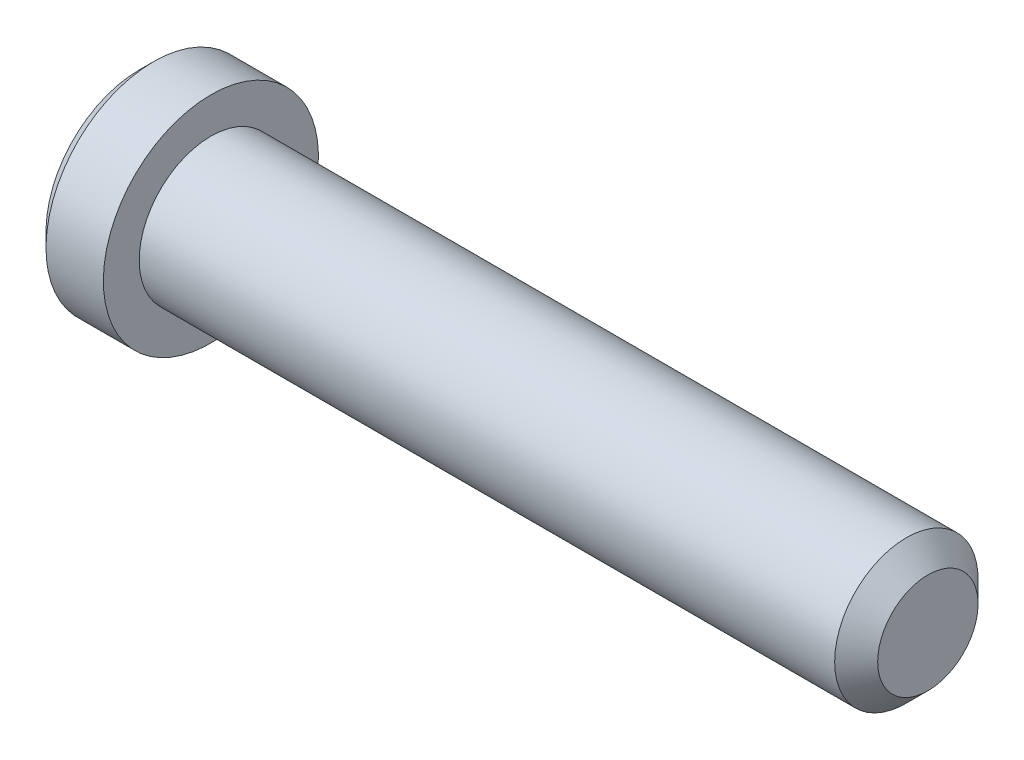
SolidWorks part; units mm, degrees
ref_plane "Front Plane" through (0, 0, 0) normal (0, 0, 1) x (1, 0, 0)
ref_plane "Top Plane" through (0, 0, 0) normal (0, 1, 0) x (1, 0, 0)
ref_plane "Right Plane" through (0, 0, 0) normal (1, 0, 0) x (0, 0, -1)
sketch "Sketch1" plane through (0, 0, 0) normal (0, 0, 1) x (1, 0, 0)
  line L0 (15.875, 0) -> (-15.875, 0) construction
  line L1 (15.875, 3.175) -> (15.875, -3.175) construction
  line L2 (-15.875, 4.7625) -> (-15.875, -4.7625) construction
  line L3 (-15.875, 4.7625) -> (-18.415, 4.7625) construction
  line L4 (-18.415, 4.7625) -> (-19.05, 4.1275) construction
  line L5 (-19.05, 4.1275) -> (-19.05, -4.1275) construction
  line L6 (-19.05, -4.1275) -> (-18.415, -4.7625) construction
  line L7 (-18.415, -4.7625) -> (-15.875, -4.7625) construction
  point P7 (-16.6624, 0)
  point P12 (10.795, -3.175)
  dimension "D1" = 45
  dimension "Dec." = 6.35
  dimension "Length" = 31.75
  dimension "Head Dia" = 9.525
  dimension "Head Height" = 3.175
  dimension "Hex Depth" = 2.3876
  dimension "Chamfer" = 0.635
  dimension "D2" = 5.08
ref_plane "Plane1" through (15.875, 0, 0) normal (1, 0, 0) x (0, 0, -1)
ref_plane "Plane2" through (-19.05, 0, 0) normal (1, 0, 0) x (0, 0, -1)
sketch "Sketch2" plane through (15.875, 0, 0) normal (1, 0, 0) x (0, 0, -1)
  circle A0 centre (0, 0) radius 3.175
extrude "Boss-Extrude1" add sketch "Sketch2" against normal up to vertex (31.75 mm away) up to point (-15.875, 0, 0)
sketch "Sketch3" plane through (15.875, 0, 0) normal (1, 0, 0) x (0, 0, -1)
  circle A0 centre (0, 0) radius 3.175 construction
  circle A1 centre (0, 0) radius 3.175
curve "Helix/Spiral1" [suppressed] pitch 1.27 height 33.02 turns 26 parameters "Pitch"=1.27
chamfer "Chamfer1" distance 0.9525 angle 45 1 edges at (15.875, 0, -3.175)
sketch "Sketch5" plane through (0, 0, 0) normal (0, 0, 1) x (1, 0, 0)
  line L0 (15.3194, 3.175) -> (16.4306, 3.175)
  line L1 (16.4306, 3.175) -> (15.9544, 2.3501)
  line L2 (15.9544, 2.3501) -> (15.7956, 2.3501)
  line L3 (15.7956, 2.3501) -> (15.3194, 3.175)
  line L4 (15.875, 2.3501) -> (15.875, 3.175) construction
  line L5 (15.5575, 2.7626) -> (16.1925, 2.7626) construction
  dimension "D1" = 60
  dimension "D2" = 0.635
  dimension "D3" = 0.1588
sweep "Cut-Sweep1" [suppressed] cut profiles "Sketch5" path "Helix/Spiral1"
sketch "Sketch4" plane through (-19.05, 0, 0) normal (1, 0, 0) x (0, 0, -1)
  line L0 (-4.7625, 0.7937) -> (4.7625, 0.7937) construction
  line L1 (0, 1.8331) -> (-1.5875, 0.9165)
  line L2 (-1.5875, 0.9165) -> (-1.5875, -0.9165)
  line L3 (-1.5875, -0.9165) -> (0, -1.8331)
  line L4 (0, -1.8331) -> (1.5875, -0.9165)
  line L5 (1.5875, -0.9165) -> (1.5875, 0.9165)
  line L6 (1.5875, 0.9165) -> (0, 1.8331)
  line L7 (0, 0) -> (0, 0.7937) construction
  circle A0 centre (0, 0) radius 1.5875 construction
  dimension "Hex Size" = 3.175
  dimension "D1" = 9.525
  dimension "D2" = 0.7937
sketch "Sketch6" plane through (0, 0, 0) normal (0, 0, 1) x (1, 0, 0)
  line L0 (-18.415, 4.7625) -> (-19.05, 4.1275) construction
  line L1 (-15.875, 4.7625) -> (-18.415, 4.7625) construction
  line L2 (-15.875, 4.7625) -> (-15.875, -4.7625) construction
  line L3 (-19.05, 4.1275) -> (-19.05, -4.1275) construction
  line L4 (-18.415, 4.7625) -> (-19.05, 4.1275)
  line L5 (-15.875, 4.7625) -> (-18.415, 4.7625)
  line L6 (-15.875, 4.7625) -> (-15.875, 0)
  line L7 (-19.05, 4.1275) -> (-19.05, 0)
  line L8 (-15.875, 0) -> (-19.05, 0) construction
  line L9 (-15.875, 0) -> (-19.05, 0)
revolve "Revolve1" add sketch "Sketch6" angle 360 about L8
extrude "Cut-Extrude1" cut sketch "Sketch4" along normal up to vertex (2.3876 mm away) up to point (-16.6624, 0, 0)
sketch "Sketch8" plane through (-19.05, 0, 0) normal (-1, 0, 0) x (0, 0, 1)
  circle A1 centre (0, 0) radius 1.8331
extrude "Cut-Extrude2" cut sketch "Sketch8" against normal through all draft 45
equation "\"D3@Helix/Spiral1\" = \"Length@Sketch1\"+\"Pitch@Helix/Spiral1\""
equation "\"D3@Sketch5\" = \"Pitch@Helix/Spiral1\"*.125"
equation "\"D2@Sketch5\" = \"Pitch@Helix/Spiral1\"*.50"
equation "\"D1@Chamfer1\" = \"Pitch@Helix/Spiral1\"*.75"
equation "\"D2@Sketch1\" = \"Pitch@Helix/Spiral1\"*4"
equation "\"D1@Sketch4\" = \"Head Dia@Sketch1\""
